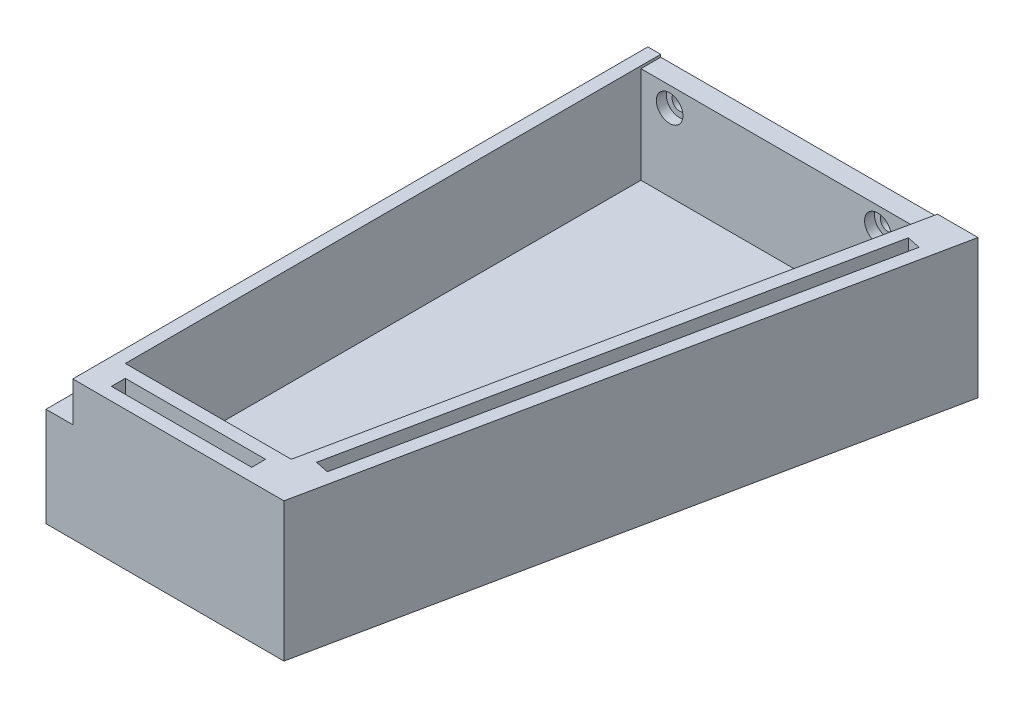
SolidWorks part; units mm, degrees
ref_plane "Front Plane" through (0, 0, 0) normal (1, 0, 0) x (0, 1, 0)
ref_plane "Top Plane" through (0, 0, 0) normal (0, 0, 1) x (0, 1, 0)
ref_plane "Right Plane" through (0, 0, 0) normal (0, 1, 0) x (-1, 0, 0)
sketch "Sketch1" plane through (0, 0, 0) normal (0, 1, 0) x (-1, 0, 0)
  line L0 (-13.4363, 2.5951) -> (16.5637, 147.5951)
  line L1 (-13.4363, -4.9049) -> (-8.4363, -4.9049)
  line L2 (-13.4363, -4.9049) -> (-13.4363, 2.5951)
  line L3 (-13.4363, 2.5951) -> (-8.4363, 2.5951)
  line L4 (-8.4363, -4.9049) -> (-8.4363, 2.5951)
  line L13 (-13.4363, 2.5951) -> (16.5637, 147.5951)
  line L14 (-13.4363, 2.5951) -> (-3.6437, 0.569)
  line L15 (-13.4363, 2.5951) -> (66.5637, 2.5951) construction
  line L16 (-13.4363, 2.5951) -> (-13.4363, 137.5951) construction
  line L17 (-13.4363, 137.5951) -> (66.5637, 137.5951) construction
  line L18 (66.5637, 2.5951) -> (66.5637, 137.5951) construction
  line L19 (66.5637, 137.5951) -> (16.5637, 137.5951)
  line L20 (66.5637, 137.5951) -> (66.5637, 147.5951)
  line L21 (66.5637, 147.5951) -> (16.5637, 147.5951)
  line L22 (16.5637, 137.5951) -> (16.5637, 147.5951)
  line L23 (16.5637, 147.5951) -> (26.3563, 145.569)
  line L24 (-3.6437, 0.569) -> (26.3563, 145.569)
  line L25 (-8.4363, 2.5951) -> (-3.2246, 2.5951)
  line L27 (-3.2246, 2.5951) -> (66.5637, 2.5951)
  line L28 (-3.2246, 2.5951) -> (-3.2246, 7.5951)
  line L29 (-3.2246, 7.5951) -> (66.5637, 7.5951)
  line L30 (66.5637, 2.5951) -> (66.5637, 7.5951)
  line L35 (66.5637, 147.5951) -> (76.5637, 147.5951)
  line L36 (66.5637, 147.5951) -> (66.5637, 2.5951)
  line L37 (66.5637, 2.5951) -> (76.5637, 2.5951)
  line L38 (76.5637, 147.5951) -> (76.5637, 2.5951)
  dimension "D1" = 7.5
  dimension "D2" = 5
  dimension "D3" = 135
  dimension "D4" = 80
  dimension "D5" = 10
  dimension "D7" = 10
  dimension "D9" = 5
  dimension "D8" = 10
  dimension "D6" = 50
extrude "Boss-Extrude1" add sketch "Sketch1" along normal blind 35 contours L24 L19 L20 L21 L23 | L19 L24 L23 L22 | L28 L29 L24 L19 L22 L0 L3 L25 | L38 L35 L20 L36 L30 L37 | L29 L28 L24 | L27 L30 L29 L24 region at (-5.7274, 0, 70.7433) region at (-20.91, 0, 142.2574) region at (-45.5816, 0, 142.6608) region at (-71.5637, 0, 75.0951) region at (2.8797, 0, 5.9284) region at (-31.9275, 0, 5.0889)
sketch "Sketch3" plane through (0, 0, 0) normal (0, -1, 0) x (1, 0, 0)
  line L0 (-76.5637, 147.5951) -> (-16.5637, 147.5951)
  line L1 (-16.5637, 147.5951) -> (13.4363, 2.5951)
  line L2 (13.4363, 2.5951) -> (-76.5637, 2.5951)
  line L3 (-76.5637, 2.5951) -> (-76.5637, 147.5951)
extrude "Boss-Extrude2" add sketch "Sketch3" against normal blind 10
sketch "Sketch4" plane through (0, 35, 0) normal (0, 1, 0) x (-1, 0, 0)
  line L0 (24.7065, 137.5951) -> (-2.1901, 7.5951)
  line L1 (24.7065, 137.5951) -> (66.5637, 137.5951)
  line L2 (24.7065, 137.5951) -> (24.7065, 147.5951)
  line L3 (24.7065, 147.5951) -> (66.5637, 147.5951)
  line L4 (66.5637, 137.5951) -> (66.5637, 147.5951)
  line L5 (24.7065, 137.5951) -> (14.9139, 139.6211)
  line L6 (-2.1901, 7.5951) -> (-11.9827, 9.6211)
  line L7 (14.9139, 139.6211) -> (-11.9827, 9.6211)
  line L9 (20.8654, 135.071) -> (-4.7142, 11.4361)
  line L10 (-4.7142, 11.4361) -> (-8.1416, 12.1453)
  line L11 (17.438, 135.7801) -> (-8.1416, 12.1453)
  line L12 (20.8654, 135.071) -> (17.438, 135.7801)
  line L13 (27.9565, 140.8451) -> (27.9565, 144.3451)
  line L14 (27.9565, 144.3451) -> (63.3137, 144.3451)
  line L15 (63.3137, 140.8451) -> (63.3137, 144.3451)
  line L16 (27.9565, 140.8451) -> (63.3137, 140.8451)
  line L17 (76.5637, 147.5951) -> (16.5637, 147.5951) construction
  line L18 (17.438, 135.7801) -> (19.8825, 147.5951)
  line L20 (20.8654, 135.071) -> (23.4566, 147.5951)
  line L21 (23.4566, 147.5951) -> (19.8825, 147.5951)
  line L22 (27.9565, 144.3451) -> (19.2101, 144.3451)
  line L23 (19.2101, 144.3451) -> (18.4859, 140.8451)
  line L24 (18.4859, 140.8451) -> (27.9565, 140.8451)
  line L25 (-13.4363, 2.5951) -> (16.5637, 147.5951) construction
  dimension "D1" = 3.25
extrude "Cut-Extrude1" cut sketch "Sketch4" against normal blind 10 contours L9 L12 L11 L10 | L13 L16 L15 L14 region at (-45.6351, 35, 142.5951) region at (-6.3619, 35, 73.6081)
sketch "Sketch5" plane through (0, 35, -3.0299) normal (0, -1, 0) x (1, 0, 0)
  line L5 (13.4363, 5.625) -> (-76.5637, 5.625) construction
  line L6 (-66.5637, 10.625) -> (2.1901, 10.625)
  line L7 (-66.5637, 10.625) -> (-66.5637, 5.625)
  line L8 (-66.5637, 5.625) -> (2.1901, 5.625)
  line L9 (2.1901, 10.625) -> (2.1901, 5.625)
  line L10 (2.1901, 10.625) -> (3.2246, 5.625)
  line L11 (2.1901, 10.625) -> (-24.7065, 140.625) construction
  line L12 (3.2246, 5.625) -> (2.1901, 5.625)
  line M9 (-66.5637, 10.625) -> (2.1901, 10.625)
  line M14 (13.4363, 5.625) -> (-76.5637, 5.625)
extrude "Cut-Extrude2" cut sketch "Sketch5" along normal blind 0.625 contours L9 L10 M14 | L9 L7 M9 M14 region at (-32.1868, 35, 5.0951) region at (2.5349, 35, 4.2617)
sketch "Sketch6" plane through (0, 0, 7.5951) normal (0, 0, 1) x (1, 0, 0)
  line L1 (-66.5637, 34.375) -> (-59.3137, 34.375) construction
  line L2 (-66.5637, 34.375) -> (-66.5637, 29.375) construction
  line L3 (-66.5637, 29.375) -> (-59.3137, 29.375) construction
  line L4 (-59.3137, 34.375) -> (-59.3137, 29.375) construction
  circle A0 centre (-59.3137, 29.375) radius 1.9
  dimension "D2" = 5
  dimension "D3" = 3.8
  dimension "D1" = 7.25
extrude "Cut-Extrude3" cut sketch "Sketch6" against normal up to next
sketch "Sketch7" plane through (0, 0, 7.5951) normal (0, 0, 1) x (1, 0, 0)
  circle A0 centre (-59.3137, 29.375) radius 3.35
  dimension "D1" = 6.7
extrude "Cut-Extrude4" cut sketch "Sketch7" against normal blind 2.5
pattern_linear "LPattern1" count 2 spacing 52.5 along (1, 0, 0) of "Cut-Extrude4", "Cut-Extrude3"
sketch "Sketch8" plane through (0, 35, 0) normal (0, 1, 0) x (-1, 0, 0)
  line L0 (76.5637, 147.5951) -> (16.5637, 147.5951) construction
  line L1 (66.5637, 2.5951) -> (69.8137, 2.5951)
  line L2 (66.5637, 2.5951) -> (66.5637, 147.5951)
  line L3 (66.5637, 147.5951) -> (69.8137, 147.5951)
  line L4 (69.8137, 2.5951) -> (69.8137, 147.5951)
  line L5 (66.5637, 2.5951) -> (76.5637, 2.5951) construction
  line L6 (76.5637, 147.5951) -> (73.3137, 147.5951)
  line L7 (76.5637, 147.5951) -> (76.5637, 2.5951)
  line L8 (76.5637, 2.5951) -> (73.3137, 2.5951)
  line L9 (73.3137, 147.5951) -> (73.3137, 2.5951)
  line L11 (73.3137, 2.5951) -> (69.8137, 2.5951)
  line L12 (73.3137, 2.5951) -> (73.3137, 147.5951)
  line L13 (73.3137, 147.5951) -> (69.8137, 147.5951)
  line L14 (69.8137, 2.5951) -> (69.8137, 147.5951)
  line M8 (66.5637, 2.5951) -> (76.5637, 2.5951)
  line M9 (76.5637, 2.5951) -> (76.5637, 147.5951)
  line M10 (76.5637, 147.5951) -> (16.5637, 147.5951)
  dimension "D1" = 3.25
  dimension "D2" = 3.25
extrude "Cut-Extrude5" cut sketch "Sketch8" against normal blind 10 contours L9 L4 M10 M8 | L9 M10 M8 M9 region at (-71.5637, 35, 75.0951) region at (-74.9387, 35, 75.0951)
equation "\"whitekey_cutout_length\"= 101.5"
equation "\"whitekey_spacing\"=1.25"
equation "\"key_mount_recess_length\"=50"
equation "\"key_mount_recess_height\"=12.5"
equation "\"key_mount_recess_depth\"=1.5"
equation "\"wall_thickness\"=10"
equation "\"guide_brace_height\"=20"
equation "\"guide_brace_thickness\"=2"
equation "\"dowel_recess_depth\"=10"
equation "\"dowel_recess_offset\"=3.25"
equation "\"dowel_insert_tolerance\"=0.1"
equation "\"base_mount_height\"=40"
equation "\"base_rear_length\"=80"
equation "\"base_front_length\"=111.5"
equation "\"screw_hole_wall_offset\"=7.25"
equation "\"screw_hole_edge_inset\"=\"dowel_recess_depth\"/2"
equation "\"screw_hole_diameter\"=3.8"
equation "\"screw_head_hole_diameter\"=6.7"
equation "\"screw_nut_hole_side_len\"=3.5"
equation "\"screw_nut_recess_offset\"=0.35"
equation "\"screw_head_and_nut_recess_depth\"=2.5"
equation "\"screw_shaft_diameter\"=3.5"
equation "\"switch_board_width\"=30"
equation "\"switch_board_thickness\"=1.6"
equation "\"switch_board_wall_offset\"=11.5"
equation "\"heatset_insert_hole_diameter\"=4.8"
equation "\"heatset_insert_hole_depth\"=3.8"
equation "\"front_rear_panel_width\"=23.75"
equation "\"front_panel_height\"=24"
equation "\"front_rear_panel_recess_depth\"=5"
equation "\"rod_diameter\"=5"
equation "\"rod_head_diameter\"=8"
equation "\"rod_length_adj\"=0.5"
equation "\"rod_insert_length\"=2.8"
equation "\"switch_black_key_mount_height\"=8"
equation "\"switch_white_key_mount_height\"=3"
equation "\"side_panel_depth\"=35"
equation "\"D5@Sketch1\"=\"wall_thickness\""
equation "\"D7@Sketch1\"=\"wall_thickness\""
equation "\"D8@Sketch1\"=\"wall_thickness\""
equation "\"D9@Sketch1\"=\"wall_thickness\"/2"
equation "\"D2@Sketch1\"=\"wall_thickness\"/2"
equation "\"D1@Sketch1\"=\"wall_thickness\"*0.75"
equation "\"D3@Sketch1\"=\"interface_panel_height\""
equation "\"D4@Sketch1\"=\"base_rear_length\""
equation "\"D1@Boss-Extrude1\"=\"side_panel_depth\""
equation "\"D1@Boss-Extrude2\"=\"wall_thickness\""
equation "\"D1@Sketch4\"=\"dowel_recess_offset\""
equation "\"D1@Cut-Extrude1\"=\"dowel_recess_depth\""
equation "\"D1@Sketch6\"=\"screw_hole_wall_offset\""
equation "\"D2@Sketch6\"=\"screw_hole_edge_inset\""
equation "\"D3@Sketch6\"=\"screw_hole_diameter\""
equation "\"D1@Sketch7\"=\"screw_head_hole_diameter\""
equation "\"D3@LPattern1\"=\"base_rear_length\"-\"wall_thickness\"-\"screw_hole_wall_offset\"*2-3"
equation "\"D1@Sketch8\"=\"dowel_recess_offset\""
equation "\"D2@Sketch8\"=\"dowel_recess_offset\""
equation "\"D1@Cut-Extrude5\"=\"front_rear_panel_recess_depth\"*2"
equation "\"D1@Cut-Extrude2\"=\"whitekey_spacing\"/2"
equation "\"interface_panel_height\"=135"
equation "\"interface_panel_roof_length\"=50"
equation "\"D6@Sketch1\"=\"interface_panel_roof_length\""
